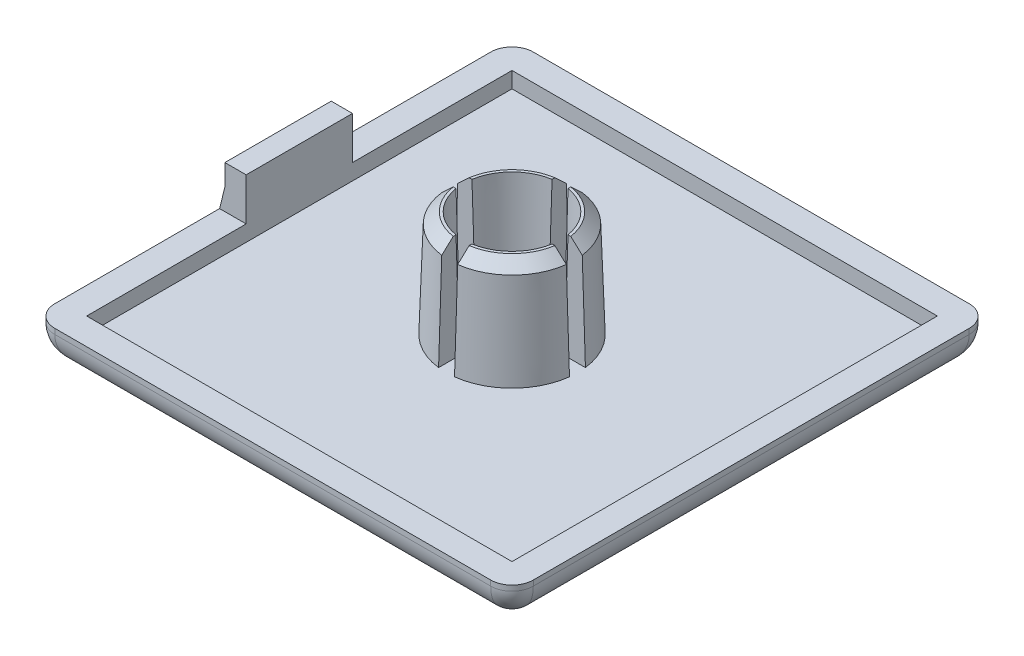
SolidWorks part; units mm, degrees
ref_plane "前视" through (0, 0, 0) normal (0, 0, 1) x (1, 0, 0)
ref_plane "上视" through (0, 0, 0) normal (0, 1, 0) x (1, 0, 0)
ref_plane "右视" through (0, 0, 0) normal (1, 0, 0) x (0, 0, -1)
sketch "草图1" plane through (0, 0, 0) normal (0, 1, 0) x (1, 0, 0)
  line L1 (-22.5, -22.5) -> (22.5, -22.5)
  line L2 (-22.5, -22.5) -> (-22.5, 22.5)
  line L3 (-22.5, 22.5) -> (22.5, 22.5)
  line L4 (22.5, -22.5) -> (22.5, 22.5)
  line L5 (-22.5, -22.5) -> (22.5, 22.5) construction
  line L6 (-22.5, 22.5) -> (22.5, -22.5) construction
  point P0 (0, 0)
  dimension "D1" = 45
  dimension "D2" = 45
extrude "凸台-拉伸1" add sketch "草图1" along normal blind 3.5
sketch "草图2" plane through (0, 3.5, 0) normal (0, 1, 0) x (1, 0, 0)
  line L1 (-20, -20) -> (20, -20)
  line L2 (-20, -20) -> (-20, 20)
  line L3 (-20, 20) -> (20, 20)
  line L4 (20, -20) -> (20, 20)
  line L5 (-20, -20) -> (20, 20) construction
  line L6 (-20, 20) -> (20, -20) construction
  point P0 (0, 0)
  dimension "D1" = 40
  dimension "D2" = 40
extrude "切除-拉伸1" cut sketch "草图2" against normal blind 1.5
fillet "圆角1" radius 2 4 edges at (-22.5, 1.75, 22.5) (22.5, 1.75, 22.5) (22.5, 1.75, -22.5) (-22.5, 1.75, -22.5)
fillet "圆角2" radius 3 8 edges at (21.9142, 0, 21.9142) (22.5, 0, 0) (21.9142, 0, -21.9142) (0, 0, -22.5) (-21.9142, 0, -21.9142) (-22.5, 0, 0) (-21.9142, 0, 21.9142) (0, 0, 22.5)
sketch "草图3" plane through (0, 3.5, 0) normal (0, 1, 0) x (1, 0, 0)
  line L1 (-22, 5) -> (-20, 5)
  line L2 (-22, 5) -> (-22, -5)
  line L3 (-22, -5) -> (-20, -5)
  line L4 (-20, 5) -> (-20, -5)
  line L5 (-20, 20) -> (-20, -20) construction
  dimension "D1" = 5
  dimension "D2" = 10
  dimension "D3" = 2
extrude "凸台-拉伸2" add sketch "草图3" along normal blind 4
sketch "草图5" plane through (0, 0, 5) normal (0, 0, 1) x (1, 0, 0)
  line L0 (-22, 7.5) -> (-22, 3.5) construction
  line L1 (-22.5, 3.5) -> (-22, 3.5)
  line L4 (-22, 3.5) -> (-22, 5.5)
  line L5 (-22, 5.5) -> (-22.5, 3.5)
extrude "凸台-拉伸3" add sketch "草图5" against normal up to surface (10 mm away) up to face at (-20.75, 6, -5)
sketch "草图6" plane through (0, 2, 0) normal (0, 1, 0) x (1, 0, 0)
  circle A0 centre (0, 0) radius 6.2
  circle A1 centre (0, 0) radius 4.25
  dimension "D1" = 12.4
  dimension "D2" = 8.5
extrude "凸台-拉伸4" add sketch "草图6" along normal blind 10 draft 1.88
chamfer "倒角1" distance 1 angle 45 1 edges at (0, 12, 5.8718) first distance on face at (0, 12, 5.8718)
sketch "草图7" plane through (0, 12, 0) normal (0, 1, 0) x (1, 0, 0)
  line L1 (-0.75, -8.4649) -> (0.75, -8.4649)
  line L2 (-0.75, -8.4649) -> (-0.75, -0.75)
  line L3 (-0.75, 8.4649) -> (0.75, 8.4649)
  line L4 (0.75, -8.4649) -> (0.75, -0.75)
  line L7 (-8.6795, 0.75) -> (-0.75, 0.75)
  line L8 (-8.6795, 0.75) -> (-8.6795, -0.75)
  line L9 (-8.6795, -0.75) -> (-0.75, -0.75)
  line L10 (8.6795, 0.75) -> (8.6795, -0.75)
  line L13 (-0.75, 0.75) -> (-0.75, 8.4649)
  line L17 (0.75, 0.75) -> (0.75, 8.4649)
  line L19 (0.75, 0.75) -> (8.6795, 0.75)
  line L20 (0.75, -0.75) -> (8.6795, -0.75)
  point P0 (0, 0)
  point P6 (0, 0)
  dimension "D1" = 1.5
  dimension "D2" = 1.5
extrude "切除-拉伸2" cut sketch "草图7" against normal up to surface (10 mm away) up to face at (0, 2, 0)
